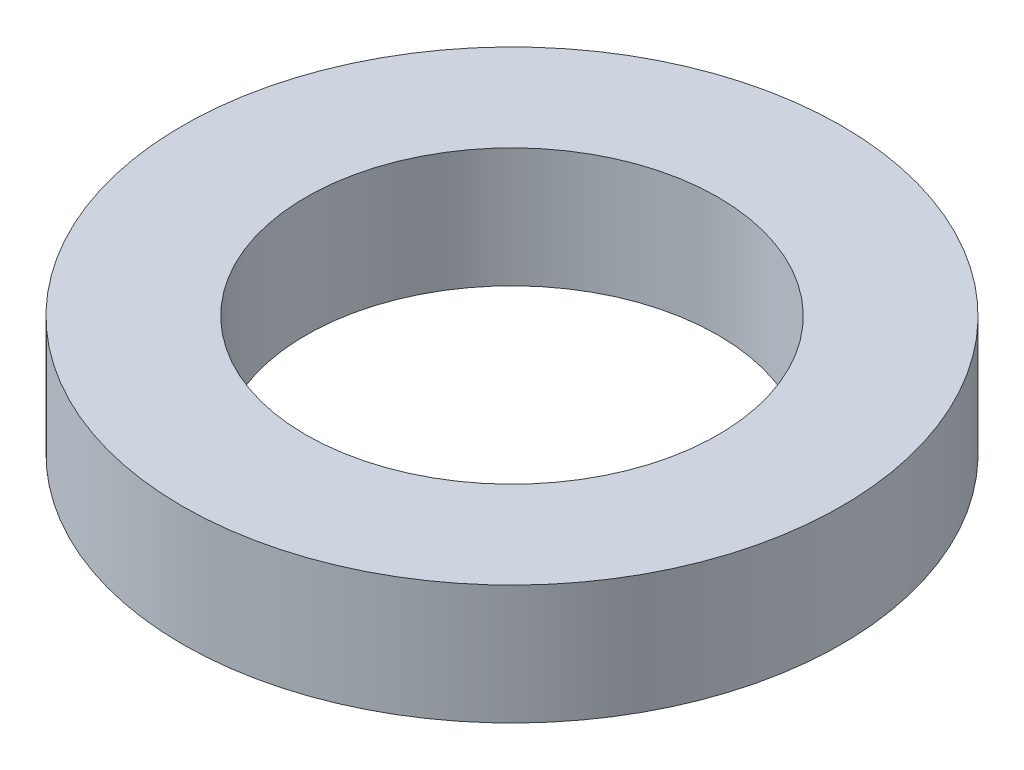
SolidWorks part; units mm, degrees
ref_plane "Front Plane" through (0, 0, 0) normal (0, 0, 1) x (1, 0, 0)
ref_plane "Top Plane" through (0, 0, 0) normal (0, 1, 0) x (1, 0, 0)
ref_plane "Right Plane" through (0, 0, 0) normal (1, 0, 0) x (0, 0, -1)
sketch "Sketch1" plane through (0, 0, 0) normal (0, 1, 0) x (1, 0, 0)
  circle A0 centre (0, 0) radius 80
  dimension "FLANGE_OD" = 160
extrude "Boss-Extrude1" add sketch "Sketch1" along normal blind 29
sketch "Sketch2" plane through (0, 0, 0) normal (0, 1, 0) x (1, 0, 0)
  circle A0 centre (0, 0) radius 50
  dimension "BORE_D" = 100
extrude "Cut-Extrude1" cut sketch "Sketch2" along normal through all
sketch "Sketch3" plane through (0, 29, 0) normal (0, 1, 0) x (1, 0, 0)
  circle A0 centre (0, 0) radius 34.4046 construction
  circle A1 centre (-34.4046, 0) radius 2.7193
  dimension "BOLT_D" = 5.4385
  dimension "BOLT_PCD" = 68.8091
extrude "Cut-Extrude2" cut sketch "Sketch3" against normal blind 24.8538 rebuild error yes
pattern_circular "CirPattern1" count 5 over 360 rebuild error yes
